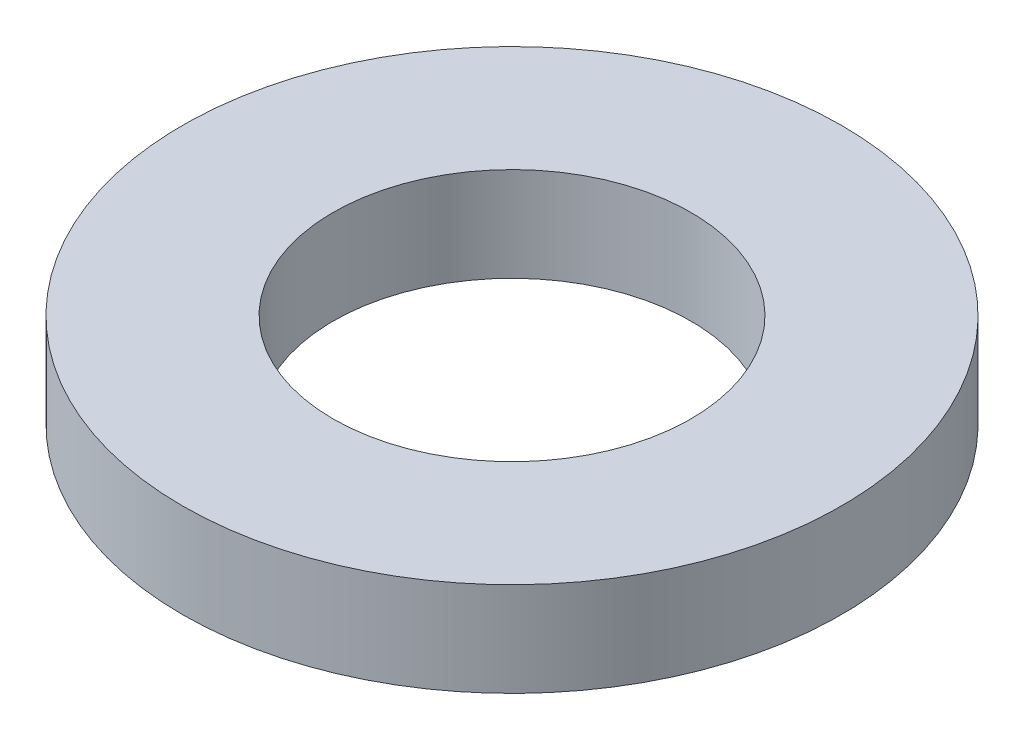
SolidWorks part; units mm, degrees
ref_plane "Front Plane" through (0, 0, 0) normal (0, 0, 1) x (1, 0, 0)
ref_plane "Top Plane" through (0, 0, 0) normal (0, 1, 0) x (1, 0, 0)
ref_plane "Right Plane" through (0, 0, 0) normal (1, 0, 0) x (0, 0, -1)
sketch "Sketch1" plane through (0, 0, 0) normal (0, 1, 0) x (1, 0, 0)
  circle A0 centre (0, 0) radius 87.5
  dimension "FLANGE_OD" = 175
extrude "Boss-Extrude1" add sketch "Sketch1" along normal blind 25
sketch "Sketch2" plane through (0, 0, 0) normal (0, 1, 0) x (1, 0, 0)
  circle A0 centre (0, 0) radius 47.5
  dimension "BORE_D" = 95
extrude "Cut-Extrude1" cut sketch "Sketch2" along normal through all
sketch "Sketch3" plane through (0, 25, 0) normal (0, 1, 0) x (1, 0, 0)
  circle A0 centre (0, 0) radius 36.2102 construction
  circle A1 centre (-36.2102, 0) radius 1.8893
  dimension "BOLT_D" = 3.7785
  dimension "BOLT_PCD" = 72.4204
extrude "Cut-Extrude2" cut sketch "Sketch3" against normal blind 24.2342 rebuild error yes
pattern_circular "CirPattern1" count 5 over 360 rebuild error yes
